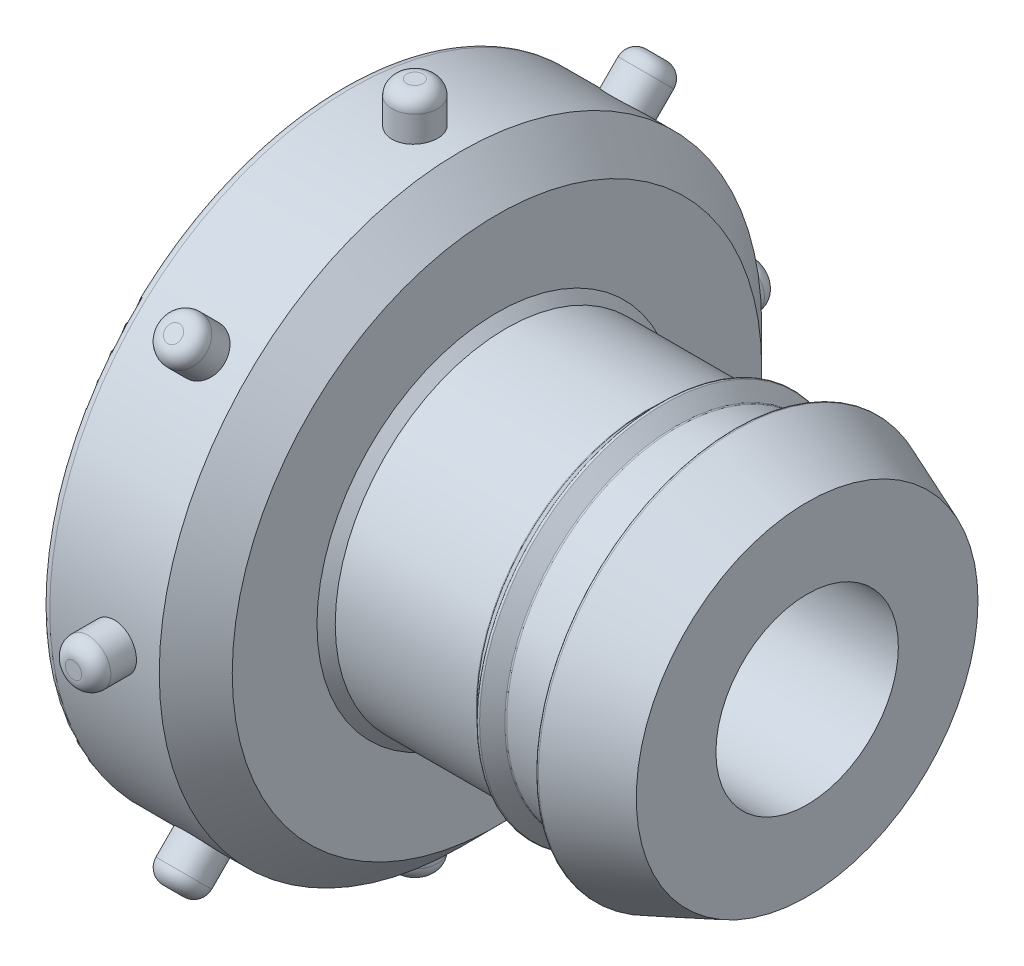
SolidWorks part; units mm, degrees
note: '?' marks a value the reader was unsure of. The reader was unsure of these and kept them because the rebuilt part matched: shared geometry of "Sketch2<3>".
ref_plane "Front Plane" through (0, 0, 0) normal (0, 0, 1) x (1, 0, 0)
ref_plane "Top Plane" through (0, 0, 0) normal (0, 1, 0) x (1, 0, 0)
ref_plane "Right Plane" through (0, 0, 0) normal (1, 0, 0) x (0, 0, -1)
sketch "Sketch1" plane through (0, 0, 0) normal (0, 1, 0) x (1, 0, 0)
  line L0 (0, 0) -> (-17, 0)
  line L1 (0, 0) -> (0, 9.365)
  line L2 (0, 9.365) -> (-3.97, 10.955)
  line L3 (-3.97, 10.955) -> (-3.97, 9.365)
  line L4 (0, 9.365) -> (-19.3321, 9.365) construction
  line L5 (-3.97, 9.365) -> (-7.15, 9.365)
  line L6 (-7.15, 9.365) -> (-7.94, 10.155)
  line L7 (-7.94, 10.155) -> (-8.73, 9.365)
  line L8 (-8.73, 9.365) -> (-17, 9.365)
  line L9 (-17, 9.365) -> (-17, 0)
  dimension "D1" = 17
  dimension "D2" = 9.365
  dimension "D3" = 1.59
  dimension "D4" = 3.97
  dimension "D5" = 7.94
  dimension "D6" = 0.79
revolve "Revolve1" add sketch "Sketch1" angle 360 about L0
sketch "Sketch2" plane through (-17, 0, 0) normal (-1, 0, 0) x (0, 0, 1)
  circle A0 centre (0, 0) radius 9.365
  circle A1 centre (0, 0) radius 9.365 construction
  circle A2 centre (0, 0) radius 5
  circle A3 centre (0, 0) radius 16.51
  circle M3 centre (0, 0) radius 9.365
  dimension "D1" = 10
  dimension "D2" = 33.02
extrude "Boss-Extrude1" add sketch "Sketch2" along normal blind 8.5 contours A3 M3 | A2 M3
ref_axis "Axis1" through (-25.5, -18.161, 0) along (0, 1, 0)?
sketch "Sketch4" plane through (-25.5, 0, 0) normal (-1, 0, 0) x (0, 0, 1)
  line L0 (0, -18.161) -> (0, 18.161) construction
  line L1 (9.09, 6.63) -> (-9.09, 6.63)
  line L2 (9.09, 6.63) -> (9.09, -6.92)
  line L3 (9.09, -6.92) -> (-9.09, -6.92)
  line L4 (-9.09, 6.63) -> (-9.09, -6.92)
  circle A1 centre (0, 0) radius 16.51 construction
  point P6 (0, 6.63)
  dimension "D1" = 18.18
  dimension "D2" = 13.55
  dimension "D3" = 6.92
extrude "Cut-Extrude1" cut sketch "Sketch4" against normal blind 7
sketch "Sketch5" plane through (-25.5, 0, 0) normal (-1, 0, 0) x (0, 0, 1)
  circle A0 centre (0, 0) radius 14.14
  dimension "D1" = 28.28
sketch "Sketch6" plane through (0, 0, 0) normal (0, 0, 1) x (1, 0, 0)
  line L0 (-25.5, 14.14) -> (-25.5, -14.14) construction
  circle A0 centre (-25.5, 14.14) radius 0.9
  point P0 (-25.5, 14.14)
  dimension "D1" = 1.8
ref_axis "Axis2" through (-35.0271, 0, 0) along (1, 0, 0)
revolve "Cut-Revolve1" cut sketch "Sketch6" angle 360 about axis through (-35.0271, 0, 0) along (1, 0, 0)
fillet "Fillet1" radius 1 1 edges at (-25.5, 0, -13.24)
ref_plane "Plane1" through (-21.5, 0, 0) normal (-1, 0, 0) x (0, 0, 1)
ref_axis "Axis3" through (-21.5, -18.161, 0) along (0, 1, 0)?
ref_plane "Plane2" through (0, 16.51, 0) normal (0, 1, 0) x (1, 0, 0)
sketch "Sketch7" plane through (0, 16.51, 0) normal (0, 1, 0) x (1, 0, 0)
  circle A0 centre (-21.5, 0) radius 1.25
  dimension "D1" = 2.5
extrude "Boss-Extrude2" add sketch "Sketch7" along normal blind 2.2 and the other way blind 2 contours A0
fillet "Fillet2" radius 0.8 1 edges at (-21.5, 18.71, 1.25)
pattern_circular "CirPattern1" count 8 over 360 about axis through (0, 0, 0) along (1, 0, 0) of "Boss-Extrude2", "Fillet2"
chamfer "Chamfer1" distance 2 angle 45 1 edges at (-17, 0, 16.51)
fillet "Fillet3" radius 0.5 1 edges at (-25.5, 0, 16.51)
fillet "Fillet4" radius 0.1 5 edges at (-8.73, 0, -9.365) (-7.94, 0, -10.155) (-7.15, 0, -9.365) (-3.97, 0, -9.365) (-3.97, 0, -10.955)
chamfer "Chamfer2" distance 0.5 angle 45 1 edges at (-17, 0, 9.365)
extrude "Cut-Extrude2" cut sketch "Sketch2<3>" against normal through all both and the other way through all contours A2
sketch "Sketch2<3>" plane through (-17, 0, 0) normal (-1, 0, 0) x (0, 0, 1) same geometry as "Sketch2"
chamfer "Chamfer3" distance 1 angle 76 1 edges at (-25.5, -6.92, 0)
sketch "Sketch8" plane through (-18.5, 0, 0) normal (-1, 0, 0) x (0, 0, 1)
  line L1 (-9.09, -6.92) -> (-5, -6.92)
  line L2 (-9.09, -6.92) -> (-9.09, 0.73)
  line L3 (-9.09, 0.73) -> (-5, 0.73)
  line L4 (-5, -6.92) -> (-5, 0.73)
  circle A0 centre (0, 0) radius 5 construction
  dimension "D1" = 7.65
extrude "Boss-Extrude3" add sketch "Sketch8" along normal blind 0.64
fillet "Fillet5" radius 0.5 2 edges at (-19.14, 0.73, -7.045) (-19.14, -3.095, -5)
equation "\"WallThick\"= 1.2'thickness of wall for printer"
equation "\"dHole\"= 3.3'diameter of screw hole"
equation "\"D3@Sketch4\"=33.02/2-9.59"
equation "\"D1@Boss-Extrude2\"=(37.42-33.02)/2"
